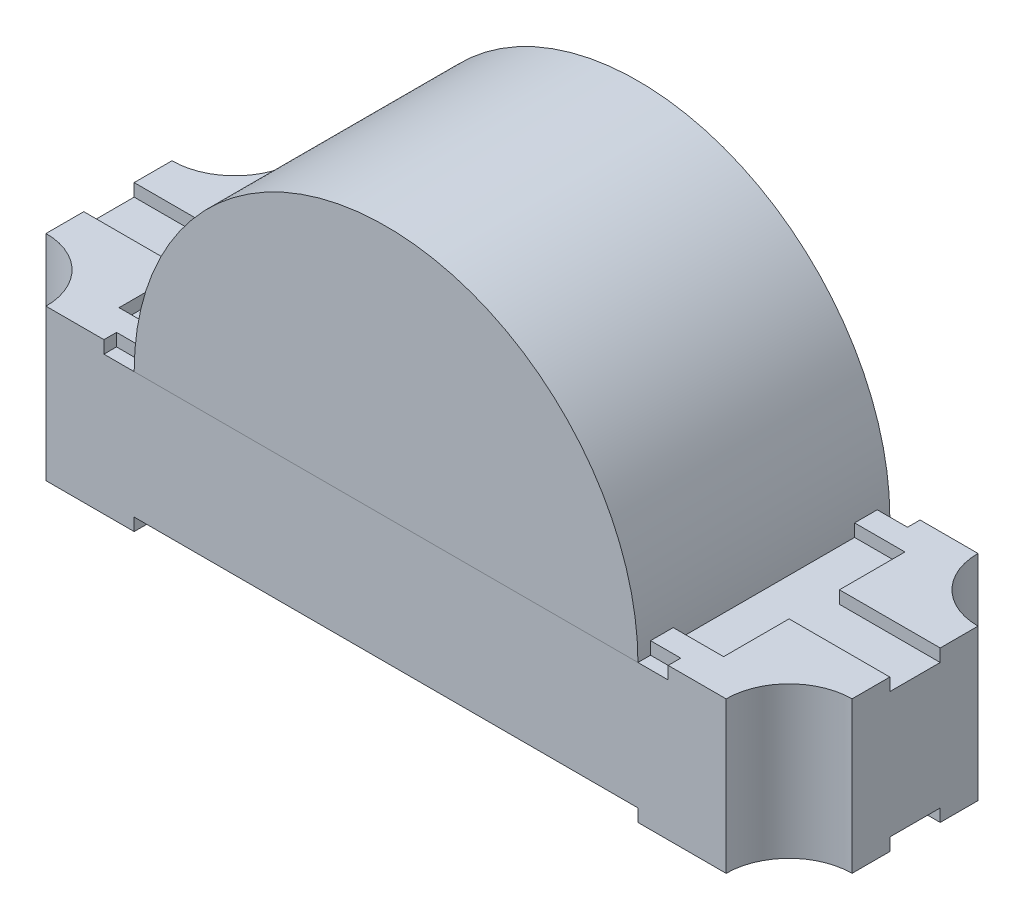
SolidWorks part; units mm, degrees
ref_plane "Front" through (0, 0, 0) normal (0, 0, 1) x (1, 0, 0)
ref_plane "Top" through (0, 0, 0) normal (0, 1, 0) x (1, 0, 0)
ref_plane "Right" through (0, 0, 0) normal (1, 0, 0) x (0, 0, -1)
sketch "Эскиз1" plane through (0, 0, 0) normal (0, 0, 1) x (1, 0, 0)
  line L0 (-1.6, 0.25) -> (-1, 0.25)
  line L1 (-1.6, 0.25) -> (1.6, 0.25) construction
  line L2 (-1.6, 0.25) -> (-1.6, -0.25)
  line L3 (-1.6, -0.25) -> (1.6, -0.25)
  line L4 (1.6, 0.25) -> (1.6, -0.25)
  line L5 (-1.6, 0.25) -> (1.6, -0.25) construction
  line L6 (-1.6, -0.25) -> (1.6, 0.25) construction
  line L7 (1.6, 0.25) -> (1, 0.25)
  line L8 (0, 0) -> (0, 1.25) construction
  arc A0 (-1, 0.25) -> (1, 0.25) centre (0, 0.25) cw
  point P0 (0, 0)
  point P11 (0, 0)
  point P12 (0, 0)
  point P13 (0, 0)
  point P14 (0, 0)
  point P15 (1.0868, 0.25)
  dimension "D1" = 0.5
  dimension "D2" = 1.5
  dimension "D3" = 3.2
  dimension "D4" = 2
extrude "Бобышка-Вытянуть1" add sketch "Эскиз1" along normal blind 1
split "Разделить1" bodies to split 101 resulting bodies 102 103 split by face at (1.3, 0.25, 0.5)
sketch "Эскиз2" plane through (0, -0.25, 0) normal (0, -1, 0) x (1, 0, 0)
  line L0 (-1.6, 1) -> (-1.6, 0) construction
  line L1 (-1.6, 0) -> (1.6, 0) construction
  line L2 (-1.6, 1) -> (1.6, 1) construction
  line L3 (1.6, 1) -> (1.6, 0) construction
  line L4 (-1.35, 0) -> (-1.6, 0)
  line L5 (-1.6, 0) -> (-1.6, 0.25)
  line L6 (-1.35, 1) -> (-1.6, 1)
  line L7 (-1.6, 1) -> (-1.6, 0.75)
  line L8 (1.6, 0.75) -> (1.6, 1)
  line L9 (1.6, 1) -> (1.35, 1)
  line L10 (1.6, 0.25) -> (1.6, 0)
  line L11 (1.6, 0) -> (1.35, 0)
  arc A0 (-1.6, 0.25) -> (-1.35, 0) centre (-1.6, 0) cw
  arc A1 (-1.6, 0.75) -> (-1.35, 1) centre (-1.6, 1) ccw
  arc A2 (1.35, 1) -> (1.6, 0.75) centre (1.6, 1) ccw
  arc A3 (1.6, 0.25) -> (1.35, 0) centre (1.6, 0) ccw
  dimension "D1" = 0.25
extrude "Вырез-Вытянуть1" cut sketch "Эскиз2" against normal up to next (0.5 mm away)
sketch "Эскиз3" plane through (0, -0.25, 0) normal (0, -1, 0) x (1, 0, 0)
  line L0 (-1, 0) -> (-1, 0.4)
  line L1 (-1.35, 0) -> (1.35, 0) construction
  line L2 (-1, 0.4) -> (-1.6, 0.4)
  line L3 (-1.6, 0.75) -> (-1.6, 0.25) construction
  line L4 (1, 0) -> (1, 0.4)
  line L5 (1, 0.4) -> (1.6, 0.4)
  line L6 (1.6, 0.75) -> (1.6, 0.25) construction
  line L7 (1.6, 0.4) -> (1.6, 0.25)
  line L8 (1.35, 0) -> (1, 0)
  line L9 (-1.6, 0.4) -> (-1.6, 0.25)
  line L10 (-1.35, 0) -> (-1, 0)
  line L11 (1, 1) -> (1, 0.95)
  line L12 (-1.35, 1) -> (1.35, 1) construction
  line L13 (1, 0.95) -> (0.295, 0.95)
  line L14 (0.295, 0.95) -> (0.295, 0.45)
  line L15 (0.295, 0.45) -> (0.17, 0.45)
  line L16 (0.17, 0.45) -> (0.17, 0)
  line L17 (0.17, 0) -> (0.67, 0)
  line L18 (0.67, 0) -> (0.67, 0.45)
  line L19 (0.67, 0.45) -> (0.545, 0.45)
  line L20 (0.545, 0.45) -> (0.545, 0.86)
  line L21 (0.545, 0.86) -> (1, 0.86)
  line L22 (1, 0.86) -> (1, 0.6)
  line L23 (1, 0.6) -> (1.6, 0.6)
  line L24 (1.6, 0.6) -> (1.6, 0.75)
  line L25 (1.35, 1) -> (1, 1)
  line L26 (-1.35, 1) -> (-1, 1)
  line L27 (-1, 1) -> (-1, 0.95)
  line L28 (-1, 0.95) -> (-0.295, 0.95)
  line L29 (-0.295, 0.95) -> (-0.295, 0.45)
  line L30 (-0.295, 0.45) -> (-0.17, 0.45)
  line L31 (-0.17, 0.45) -> (-0.17, 0)
  line L32 (-0.17, 0) -> (-0.67, 0)
  line L33 (-0.67, 0) -> (-0.67, 0.45)
  line L34 (-0.67, 0.45) -> (-0.545, 0.45)
  line L35 (-0.545, 0.45) -> (-0.545, 0.86)
  line L36 (-0.545, 0.86) -> (-1, 0.86)
  line L37 (-1, 0.86) -> (-1, 0.6)
  line L38 (-1, 0.6) -> (-1.6, 0.6)
  line L39 (-1.6, 0.6) -> (-1.6, 0.75)
  line L40 (-0.17, 0) -> (0.17, 0) construction
  arc A0 (1.6, 0.25) -> (1.35, 0) centre (1.6, 0) ccw
  arc A1 (-1.6, 0.25) -> (-1.35, 0) centre (-1.6, 0) cw
  arc A2 (1.6, 0.75) -> (1.35, 1) centre (1.6, 1) cw
  arc A3 (-1.6, 0.75) -> (-1.35, 1) centre (-1.6, 1) ccw construction
  arc A4 (-1.6, 0.75) -> (-1.35, 1) centre (-1.6, 1) ccw
  point P63 (0, 0)
  point P64 (0.2957, 0.5043)
  point P65 (0.4709, 0.8638)
  point P66 (0.4787, 0.7827)
  point P67 (-0.3541, 0.9324)
  point P68 (-0.295, 0.482)
  dimension "D1" = 2
  dimension "D2" = 0.2
  dimension "D3" = 1.34
  dimension "D4" = 0.34
  dimension "D5" = 0.25
  dimension "D6" = 0.45
  dimension "D7" = 0.09
  dimension "D8" = 0.05
extrude "Бобышка-Вытянуть2" add sketch "Эскиз3" along normal blind 0.05
sketch "Эскиз4" plane through (0, 0.25, 0) normal (0, 1, 0) x (1, 0, 0)
  line L0 (1.6, -0.4) -> (1.2, -0.4)
  line L1 (1.6, -0.75) -> (1.6, -0.25) construction
  line L2 (1.2, -0.4) -> (1.2, -0.14)
  line L3 (1.2, -0.14) -> (1, -0.14)
  line L4 (1, -0.14) -> (1, -0.05)
  line L5 (1, -0.05) -> (1.12, -0.05)
  line L6 (1.12, -0.05) -> (1.12, 0)
  line L7 (1.35, 0) -> (-1.35, 0) construction
  line L8 (1.12, 0) -> (1.35, 0)
  line L9 (1.6, -0.25) -> (1.6, -0.4)
  line L10 (1.6, -0.6) -> (1.2, -0.6)
  line L11 (1.2, -0.6) -> (1.2, -0.86)
  line L12 (1.2, -0.86) -> (1, -0.86)
  line L13 (1, -0.86) -> (1, -0.95)
  line L14 (1, -0.95) -> (1.12, -0.95)
  line L15 (1.12, -1) -> (1.12, -0.95)
  line L16 (1.35, -1) -> (-1.35, -1) construction
  line L17 (1.12, -1) -> (1.35, -1)
  line L18 (1.6, -0.75) -> (1.6, -0.6)
  line L19 (-1.6, -0.25) -> (-1.6, -0.4)
  line L20 (-1.6, -0.75) -> (-1.6, -0.25) construction
  line L21 (-1.6, -0.4) -> (-1.2, -0.4)
  line L22 (-1.2, -0.4) -> (-1.2, -0.14)
  line L23 (-1.2, -0.14) -> (-1, -0.14)
  line L24 (-1, -0.14) -> (-1, -0.05)
  line L25 (-1.12, -0.05) -> (-1, -0.05)
  line L26 (-1.12, -0.05) -> (-1.12, 0)
  line L27 (-1.12, 0) -> (-1.35, 0)
  line L28 (-1.35, -1) -> (-1.12, -1)
  line L29 (-1.12, -1) -> (-1.12, -0.95)
  line L30 (-1.12, -0.95) -> (-1, -0.95)
  line L31 (-1, -0.95) -> (-1, -0.86)
  line L32 (-1, -0.86) -> (-1.2, -0.86)
  line L33 (-1.2, -0.86) -> (-1.2, -0.6)
  line L34 (-1.2, -0.6) -> (-1.6, -0.6)
  line L35 (-1.6, -0.6) -> (-1.6, -0.75)
  arc A0 (1.35, 0) -> (1.6, -0.25) centre (1.6, 0) ccw
  arc A1 (1.35, -1) -> (1.6, -0.75) centre (1.6, -1) cw
  arc A2 (-1.35, 0) -> (-1.6, -0.25) centre (-1.6, 0) cw
  arc A3 (-1.6, -0.75) -> (-1.35, -1) centre (-1.6, -1) cw
  point P57 (1.2649, -0.4)
  point P61 (0, 0)
  dimension "D1" = 0.4
  dimension "D2" = 0.12
extrude "Бобышка-Вытянуть4" add sketch "Эскиз4" along normal blind 0.05
